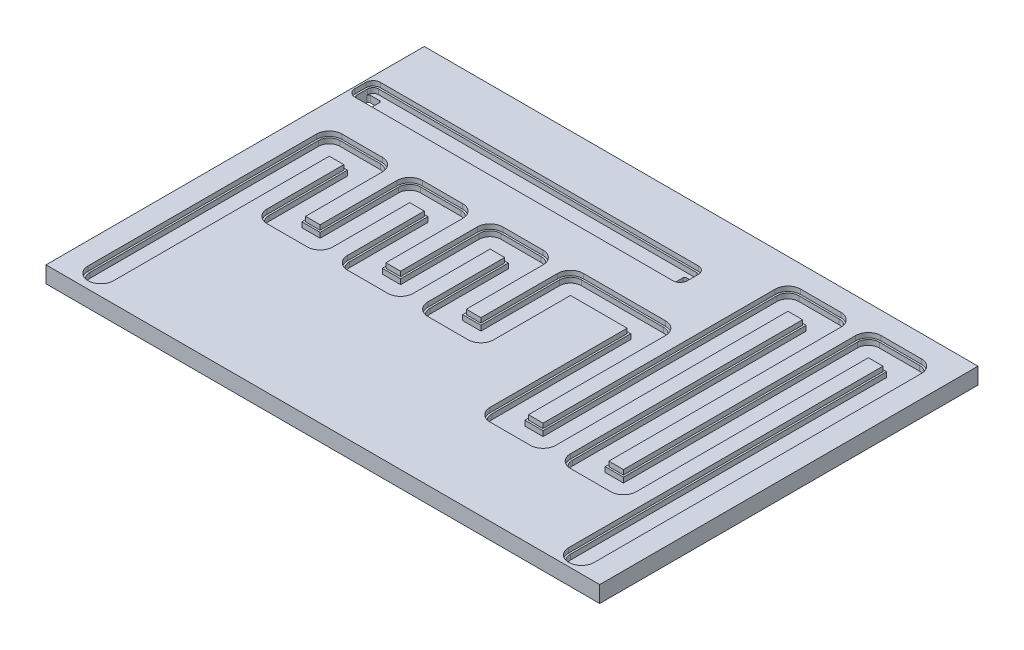
SolidWorks part; units mm, degrees
ref_plane "前视基准面" through (0, 0, 0) normal (0, 0, 1) x (1, 0, 0)
ref_plane "上视基准面" through (0, 0, 0) normal (0, 1, 0) x (1, 0, 0)
ref_plane "右视基准面" through (0, 0, 0) normal (1, 0, 0) x (0, 0, -1)
sketch "草图1" plane through (0, 0, 0) normal (0, 1, 0) x (1, 0, 0)
  line L0 (5, -195) -> (5, -165)
  line L1 (0, 0) -> (1515, 0)
  line L2 (0, 0) -> (0, -1035)
  line L3 (0, -1035) -> (1515, -1035)
  line L4 (1515, 0) -> (1515, -1035)
  line L5 (25, -145) -> (895, -145)
  line L6 (915, -165) -> (915, -195)
  line L7 (895, -215) -> (25, -215)
  line L8 (-125.9274, -180) -> (1036.3031, -180) construction
  line L9 (25, -150) -> (895, -150)
  line L10 (910, -165) -> (910, -195)
  line L11 (895, -210) -> (25, -210)
  line L12 (10, -195) -> (10, -165)
  line L13 (60, -980) -> (60, -355)
  line L14 (40, -197.5) -> (15, -197.5)
  line L15 (45, -192.5) -> (45, -167.5)
  line L16 (40, -162.5) -> (15, -162.5)
  line L17 (10, -192.5) -> (10, -167.5)
  line L18 (45, -197.5) -> (10, -162.5) construction
  line L19 (45, -162.5) -> (10, -197.5) construction
  line L20 (905, -197.5) -> (880, -197.5)
  line L21 (910, -192.5) -> (910, -167.5)
  line L22 (905, -162.5) -> (880, -162.5)
  line L23 (875, -192.5) -> (875, -167.5)
  line L24 (910, -197.5) -> (875, -162.5) construction
  line L25 (910, -162.5) -> (875, -197.5) construction
  line L26 (95, -320) -> (205, -320)
  line L27 (240, -355) -> (240, -565)
  line L28 (240, -565) -> (280, -565)
  line L29 (280, -565) -> (280, -355)
  line L30 (315, -320) -> (425, -320)
  line L31 (460, -355) -> (460, -565)
  line L32 (460, -565) -> (500, -565)
  line L33 (500, -565) -> (500, -355)
  line L34 (535, -320) -> (645, -320)
  line L35 (680, -355) -> (680, -565)
  line L36 (680, -565) -> (720, -565)
  line L37 (720, -565) -> (720, -355)
  line L38 (755, -320) -> (980, -320)
  line L39 (1015, -355) -> (1015, -730)
  line L40 (1015, -730) -> (1055, -730)
  line L41 (1055, -730) -> (1055, -95)
  line L42 (1090, -60) -> (1200, -60)
  line L43 (1235, -95) -> (1235, -730)
  line L44 (1235, -730) -> (1275, -730)
  line L45 (1275, -730) -> (1275, -95)
  line L46 (1310, -60) -> (1420, -60)
  line L47 (1455, -95) -> (1455, -990)
  line L48 (1455, -990) -> (1385, -990) construction
  line L49 (1385, -990) -> (1385, -130)
  line L50 (1385, -130) -> (1345, -130)
  line L51 (1345, -130) -> (1345, -765)
  line L52 (1310, -800) -> (1200, -800)
  line L53 (1165, -765) -> (1165, -130)
  line L54 (1165, -130) -> (1125, -130)
  line L55 (1125, -130) -> (1125, -765)
  line L56 (1090, -800) -> (980, -800)
  line L57 (945, -765) -> (945, -390)
  line L58 (945, -390) -> (790, -390)
  line L59 (790, -390) -> (790, -600)
  line L60 (755, -635) -> (645, -635)
  line L61 (610, -600) -> (610, -390)
  line L62 (610, -390) -> (570, -390)
  line L63 (570, -390) -> (570, -600)
  line L64 (535, -635) -> (425, -635)
  line L65 (390, -600) -> (390, -390)
  line L66 (390, -390) -> (350, -390)
  line L67 (350, -390) -> (350, -600)
  line L68 (315, -635) -> (205, -635)
  line L69 (170, -600) -> (170, -390)
  line L70 (170, -390) -> (130, -390)
  line L71 (130, -390) -> (130, -980)
  line L72 (130, -980) -> (60, -980) construction
  line L73 (1390, -990) -> (1390, -125)
  line L74 (1390, -125) -> (1340, -125)
  line L75 (1340, -125) -> (1340, -765)
  line L76 (1310, -795) -> (1200, -795)
  line L77 (1170, -765) -> (1170, -125)
  line L78 (1170, -125) -> (1120, -125)
  line L79 (1120, -125) -> (1120, -765)
  line L80 (1090, -795) -> (980, -795)
  line L81 (950, -765) -> (950, -385)
  line L82 (950, -385) -> (785, -385)
  line L83 (785, -385) -> (785, -600)
  line L84 (755, -630) -> (645, -630)
  line L85 (615, -600) -> (615, -385)
  line L86 (615, -385) -> (565, -385)
  line L87 (565, -385) -> (565, -600)
  line L88 (535, -630) -> (425, -630)
  line L89 (395, -600) -> (395, -385)
  line L90 (395, -385) -> (345, -385)
  line L91 (345, -385) -> (345, -600)
  line L92 (315, -630) -> (205, -630)
  line L93 (175, -600) -> (175, -385)
  line L94 (175, -385) -> (125, -385)
  line L95 (125, -385) -> (125, -980)
  line L96 (65, -980) -> (65, -355)
  line L97 (95, -325) -> (205, -325)
  line L98 (235, -355) -> (235, -570)
  line L99 (235, -570) -> (285, -570)
  line L100 (285, -570) -> (285, -355)
  line L101 (315, -325) -> (425, -325)
  line L102 (455, -355) -> (455, -570)
  line L103 (455, -570) -> (505, -570)
  line L104 (505, -570) -> (505, -355)
  line L105 (535, -325) -> (645, -325)
  line L106 (675, -355) -> (675, -570)
  line L107 (675, -570) -> (725, -570)
  line L108 (725, -570) -> (725, -355)
  line L109 (755, -325) -> (980, -325)
  line L110 (1010, -355) -> (1010, -735)
  line L111 (1010, -735) -> (1060, -735)
  line L112 (1060, -735) -> (1060, -95)
  line L113 (1090, -65) -> (1200, -65)
  line L114 (1230, -95) -> (1230, -735)
  line L115 (1230, -735) -> (1280, -735)
  line L116 (1280, -735) -> (1280, -95)
  line L117 (1310, -65) -> (1420, -65)
  line L118 (1450, -95) -> (1450, -990)
  arc A0 (5, -195) -> (25, -215) centre (25, -195) ccw
  arc A1 (5, -165) -> (25, -145) centre (25, -165) cw
  arc A2 (915, -195) -> (895, -215) centre (895, -195) cw
  arc A3 (895, -145) -> (915, -165) centre (895, -165) cw
  arc A4 (895, -150) -> (910, -165) centre (895, -165) cw
  arc A5 (910, -195) -> (895, -210) centre (895, -195) cw
  arc A6 (10, -195) -> (25, -210) centre (25, -195) ccw
  arc A7 (10, -165) -> (25, -150) centre (25, -165) cw
  arc A10 (205, -635) -> (170, -600) centre (205, -600) cw
  arc A11 (350, -600) -> (315, -635) centre (315, -600) cw
  arc A12 (425, -635) -> (390, -600) centre (425, -600) cw
  arc A13 (570, -600) -> (535, -635) centre (535, -600) cw
  arc A14 (645, -635) -> (610, -600) centre (645, -600) cw
  arc A15 (790, -600) -> (755, -635) centre (755, -600) cw
  arc A16 (980, -800) -> (945, -765) centre (980, -765) cw
  arc A17 (1125, -765) -> (1090, -800) centre (1090, -765) cw
  arc A18 (1200, -800) -> (1165, -765) centre (1200, -765) cw
  arc A19 (1345, -765) -> (1310, -800) centre (1310, -765) cw
  arc A20 (1420, -60) -> (1455, -95) centre (1420, -95) cw
  arc A21 (1275, -95) -> (1310, -60) centre (1310, -95) cw
  arc A22 (1200, -60) -> (1235, -95) centre (1200, -95) cw
  arc A23 (1055, -95) -> (1090, -60) centre (1090, -95) cw
  arc A24 (980, -320) -> (1015, -355) centre (980, -355) cw
  arc A25 (720, -355) -> (755, -320) centre (755, -355) cw
  arc A26 (645, -320) -> (680, -355) centre (645, -355) cw
  arc A27 (500, -355) -> (535, -320) centre (535, -355) cw
  arc A28 (425, -320) -> (460, -355) centre (425, -355) cw
  arc A29 (280, -355) -> (315, -320) centre (315, -355) cw
  arc A30 (205, -320) -> (240, -355) centre (205, -355) cw
  arc A31 (60, -355) -> (95, -320) centre (95, -355) cw
  arc A32 (1340, -765) -> (1310, -795) centre (1310, -765) cw
  arc A33 (1200, -795) -> (1170, -765) centre (1200, -765) cw
  arc A34 (1120, -765) -> (1090, -795) centre (1090, -765) cw
  arc A35 (980, -795) -> (950, -765) centre (980, -765) cw
  arc A36 (785, -600) -> (755, -630) centre (755, -600) cw
  arc A37 (645, -630) -> (615, -600) centre (645, -600) cw
  arc A38 (565, -600) -> (535, -630) centre (535, -600) cw
  arc A39 (425, -630) -> (395, -600) centre (425, -600) cw
  arc A40 (345, -600) -> (315, -630) centre (315, -600) cw
  arc A41 (205, -630) -> (175, -600) centre (205, -600) cw
  arc A42 (65, -355) -> (95, -325) centre (95, -355) cw
  arc A43 (205, -325) -> (235, -355) centre (205, -355) cw
  arc A44 (285, -355) -> (315, -325) centre (315, -355) cw
  arc A45 (425, -325) -> (455, -355) centre (425, -355) cw
  arc A46 (505, -355) -> (535, -325) centre (535, -355) cw
  arc A47 (645, -325) -> (675, -355) centre (645, -355) cw
  arc A48 (725, -355) -> (755, -325) centre (755, -355) cw
  arc A49 (980, -325) -> (1010, -355) centre (980, -355) cw
  arc A50 (1060, -95) -> (1090, -65) centre (1090, -95) cw
  arc A51 (1200, -65) -> (1230, -95) centre (1200, -95) cw
  arc A52 (1280, -95) -> (1310, -65) centre (1310, -95) cw
  arc A53 (1420, -65) -> (1450, -95) centre (1420, -95) cw
  arc A54 (60, -980) -> (130, -980) centre (95, -980) ccw
  arc A55 (1390, -990) -> (1450, -990) centre (1420, -990) ccw
  arc A56 (910, -167.5) -> (905, -162.5) centre (905, -167.5) ccw
  arc A57 (905, -197.5) -> (910, -192.5) centre (905, -192.5) ccw
  arc A58 (880, -197.5) -> (875, -192.5) centre (880, -192.5) cw
  arc A59 (880, -162.5) -> (875, -167.5) centre (880, -167.5) ccw
  arc A60 (15, -162.5) -> (10, -167.5) centre (15, -167.5) ccw
  arc A61 (15, -197.5) -> (10, -192.5) centre (15, -192.5) cw
  arc A62 (40, -197.5) -> (45, -192.5) centre (40, -192.5) ccw
  arc A63 (45, -167.5) -> (40, -162.5) centre (40, -167.5) ccw
  arc A65 (1385, -990) -> (1455, -990) centre (1420, -990) ccw
  arc A66 (65, -980) -> (125, -980) centre (95, -980) ccw
  point P31 (27.5, -180)
  point P36 (892.5, -180)
  point P89 (350, -495)
  point P90 (790, -495)
  point P91 (1035, -800)
  point P92 (150, -390)
  point P93 (280, -460)
  point P94 (1365, -60)
  point P95 (95, -980)
  point P96 (1420, -990)
  dimension "D7" = 20
  dimension "D51" = 35
  dimension "D55" = 5
  dimension "D54" = 35
  dimension "D1" = 1515
  dimension "D2" = 1035
  dimension "D3" = 180
  dimension "D4" = 70
  dimension "D5" = 5
  dimension "D6" = 910
  dimension "D9" = 35
  dimension "D10" = 35
  dimension "D11" = 35
  dimension "D12" = 35
  dimension "D13" = 865
  dimension "D14" = 60
  dimension "D15" = 70
  dimension "D16" = 70
  dimension "D17" = 70
  dimension "D18" = 70
  dimension "D19" = 70
  dimension "D20" = 70
  dimension "D21" = 70
  dimension "D22" = 70
  dimension "D23" = 70
  dimension "D24" = 70
  dimension "D25" = 70
  dimension "D26" = 70
  dimension "D27" = 400
  dimension "D28" = 70
  dimension "D29" = 70
  dimension "D30" = 70
  dimension "D31" = 70
  dimension "D32" = 70
  dimension "D33" = 245
  dimension "D34" = 70
  dimension "D35" = 70
  dimension "D36" = 295
  dimension "D37" = 40
  dimension "D38" = 40
  dimension "D39" = 40
  dimension "D40" = 40
  dimension "D41" = 40
  dimension "D42" = 40
  dimension "D43" = 40
  dimension "D44" = 40
  dimension "D45" = 40
  dimension "D46" = 40
  dimension "D47" = 235
  dimension "D48" = 975
  dimension "D49" = 55
  dimension "D50" = 45
  dimension "D52" = 5
  dimension "D8" = 5
extrude "凸台-拉伸1" add sketch "草图1" against normal blind 45 contours L3 L4 L1 L2
extrude "切除-拉伸1" cut sketch "草图1<3>" against normal blind 13 contours L7 A0 L0 A1 L5 A3 L6 A2
sketch "草图1<3>" plane through (0, 0, 0) normal (0, 1, 0) x (1, 0, 0) same geometry as "草图1"
extrude "切除-拉伸2" cut sketch "草图1<5>" against normal blind 27 contours L9 A4 L10 A5 L11 A6 L12 A7
sketch "草图1<5>" plane through (0, 0, 0) normal (0, 1, 0) x (1, 0, 0) same geometry as "草图1"
extrude "切除-拉伸3" cut sketch "草图1<6>" against normal blind 45 contours L15 A63 L16 A60 L17 A61 L14 A62 | L23 A59 L22 A56 L21 A57 L20 A58
sketch "草图1<6>" plane through (0, 0, 0) normal (0, 1, 0) x (1, 0, 0) same geometry as "草图1"
extrude "切除-拉伸5" cut sketch "草图1<9>" against normal blind 13 contours L71 A54 L13 A31 L26 A30 L27 L28 L29 A29 L30 A28 L31 L32 L33 A27 L34 A26 L35 L36 L37 A25 L38 A24 L39 L40 L41 A23 L42 A22 L43 L44 L45 A21 L46 A20 L47 A65 L49 L50 L51 A19 L52 A18 L53 L54 L55 A17 L56 A16 L57 L58 L59 A15 L60 A14 L61 L62 L63 A13 L64 A12 L65 L66 L67 A11 L68 A10 L69 L70
sketch "草图1<9>" plane through (0, 0, 0) normal (0, 1, 0) x (1, 0, 0) same geometry as "草图1"
extrude "切除-拉伸6" cut sketch "草图1<10>" against normal blind 27 contours L73 L74 L75 A32 L76 A33 L77 L78 L79 A34 L80 A35 L81 L82 L83 A36 L84 A37 L85 L86 L87 A38 L88 A39 L89 L90 L91 A40 L92 A41 L93 L94 L95 A66 L96 A42 L97 A43 L98 L99 L100 A44 L101 A45 L102 L103 L104 A46 L105 A47 L106 L107 L108 A48 L109 A49 L110 L111 L112 A50 L113 A51 L114 L115 L116 A52 L117 A53 L118 A55
sketch "草图1<10>" plane through (0, 0, 0) normal (0, 1, 0) x (1, 0, 0) same geometry as "草图1"
sketch "草图3" plane through (0, 0, 0) normal (0, 1, 0) x (1, 0, 0)
  line L0 (0, -1035) -> (1515, -1035) construction
  circle A0 centre (95, -990) radius 10.25
  circle A1 centre (1420, -1007.5) radius 10.25
  dimension "D1" = 20.5
  dimension "D2" = 45
  dimension "D3" = 27.5
extrude "切除-拉伸7" cut sketch "草图3" against normal blind 45
